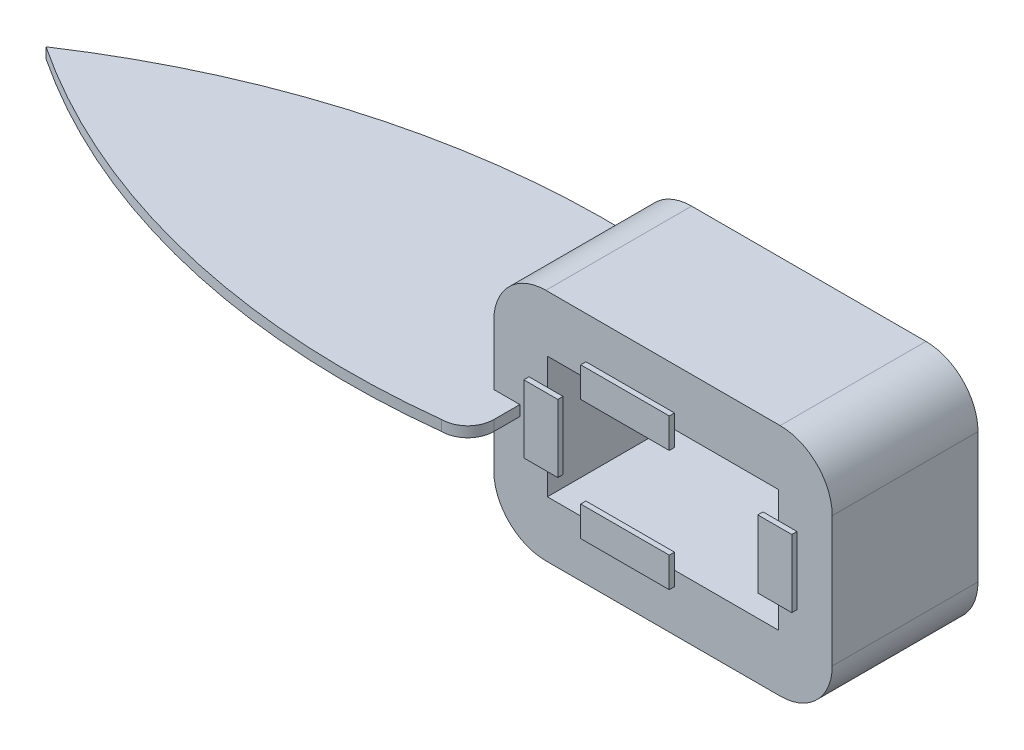
SolidWorks part; units mm, degrees
other "標示1"
sketch "草圖23" plane through (5.0653, 22.5, 33.0476) normal (0.0778, 0.9965, 0.0321) x (0.9968, -0.077, -0.0229)
ref_plane "前基準面" through (0, 0, 0) normal (0, 0, 1) x (1, 0, 0)
ref_plane "上基準面" through (0, 0, 0) normal (0, 1, 0) x (1, 0, 0)
ref_plane "右基準面" through (0, 0, 0) normal (1, 0, 0) x (0, 0, -1)
sketch "草圖1" plane through (0, 0, 0) normal (0, 0, 1) x (1, 0, 0)
  line L0 (-9.02, 0) -> (7.9922, 0) construction
  line L2 (-59.9347, 22.5) -> (5.0653, 22.5)
  line L3 (-59.9347, 22.5) -> (-59.9347, -22.5)
  line L4 (-59.9347, -22.5) -> (5.0653, -22.5)
  line L5 (5.0653, 22.5) -> (5.0653, -22.5)
  dimension "D1" = 45
  dimension "D2" = 22.5
  dimension "D3" = 65
extrude "填料-伸長1" add sketch "草圖1" along normal blind 28
sketch "草圖2" plane through (0, 0, 0) normal (0, 0, 1) x (1, 0, 0)
  line L0 (-59.9347, 0) -> (5.361, 0) construction
  line L1 (-59.9347, 22.5) -> (-59.9347, -22.5) construction
  line L2 (-27.4347, 22.5) -> (-27.4347, -22.5) construction
  line L3 (5.0653, 22.5) -> (-59.9347, 22.5) construction
  line L4 (-59.9347, -22.5) -> (5.0653, -22.5) construction
  line L6 (-49.6347, 11.7) -> (-5.2347, 11.7)
  line L7 (-49.6347, 11.7) -> (-49.6347, -11.7)
  line L8 (-49.6347, -11.7) -> (-5.2347, -11.7)
  line L9 (-5.2347, 11.7) -> (-5.2347, -11.7)
  dimension "D1" = 44.4
  dimension "D2" = 23.4
  dimension "D3" = 10.3
  dimension "D4" = 10.8
extrude "除料-伸長1" cut sketch "草圖2" along normal blind 39
ref_plane "平面1" through (0, 0, 28) normal (0, 0, 1) x (1, 0, 0)
sketch "草圖3" plane through (0, 0, 28) normal (0, 0, 1) x (1, 0, 0)
  line L0 (-59.9347, 22.5) -> (-59.9347, -22.5) construction
  line L2 (-59.9347, 12) -> (-55.9347, 12)
  line L3 (-59.9347, 12) -> (-59.9347, -12)
  line L4 (-59.9347, -12) -> (-55.9347, -12)
  line L5 (-55.9347, 12) -> (-55.9347, -12)
  line L8 (-5.2347, -11.7) -> (-49.6347, -11.7) construction
  dimension "D1" = 4
  dimension "D2" = 24
  dimension "D3" = 0.3
ref_plane "平面2" through (-59.9347, 0, 0) normal (-1, 0, 0) x (0, 0, 1)
sketch "草圖6" plane through (0, 0, 28) normal (0, 0, 1) x (1, 0, 0)
  line L0 (-15.2347, 0.3) -> (5.0653, -22.5)
  line L1 (-5.2347, 11.7) -> (-5.2347, -11.7) construction
  line L2 (-5.2347, -11.7) -> (-49.6347, -11.7) construction
  line L3 (-15.2347, 0.3) -> (-15.2347, -22.5)
  line L4 (-59.9347, -22.5) -> (5.0653, -22.5) construction
  line L5 (-15.2347, -22.5) -> (5.0653, -22.5)
  dimension "D1" = 10
  dimension "D2" = 12
ref_plane "平面4" through (0, 0, 0) normal (0, 0, -1) x (-1, 0, 0)
fillet "圓角1" radius 10 1 edges at (-59.9347, -22.5, 14) type face fillet first side face at (-59.9347, 0, 14) second side face at (-27.4347, -22.5, 14)
fillet "圓角2" radius 10 1 edges at (-59.9347, 22.5, 14) type face fillet first side face at (-27.4347, 22.5, 14) second side face at (-59.9347, 5, 14)
fillet "圓角3" radius 10 1 edges at (5.0653, 22.5, 14) type face fillet first side face at (-22.4347, 22.5, 14) second side face at (5.0653, 0, 14)
fillet "圓角4" radius 10 1 edges at (5.0653, -22.5, 14) type face fillet first side face at (-22.4347, -22.5, 14) second side face at (5.0653, -5, 14)
ref_plane "平面6" through (0, 0, 29) normal (0, 0, 1) x (1, 0, 0)
sketch "草圖10" plane through (0, 0, 29) normal (0, 0, 1) x (1, 0, 0)
  line L6 (-49.6347, 0) -> (-4.2092, 0) construction
  line L7 (-49.6347, -11.7) -> (-49.6347, 11.7) construction
  line L8 (-27.4347, -11.7) -> (-27.4347, 19.297) construction
  line L9 (-5.2347, -11.7) -> (-49.6347, -11.7) construction
  line L11 (-49.6347, 6.5) -> (-53.1651, 6.5)
  line L14 (-53.1651, 6.5) -> (-53.1651, -6.5)
  line L17 (-49.6347, 6.5) -> (-46.6347, 6.5)
  line L18 (-46.6347, 6.5) -> (-46.6347, -6.5)
  line L20 (-42.2347, -11.7) -> (-42.2347, -8.7)
  line L25 (-42.2347, -11.7) -> (-42.2347, -14.4546)
  line L27 (-8.2347, 6.5) -> (-8.2347, -6.5)
  line L28 (-8.2347, -6.5) -> (-5.2347, -6.5)
  line L29 (-5.2347, -6.5) -> (-1.7043, -6.5)
  line L30 (-1.7043, 6.5) -> (-1.7043, -6.5)
  line L32 (-25.2347, 8.7) -> (-25.2347, 14.4546)
  line L33 (-25.2347, -14.4546) -> (-25.2347, -8.7)
  line L34 (-25.2347, -14.4546) -> (-42.2347, -14.4546)
  line L35 (-25.2347, -8.7) -> (-42.2347, -8.7)
  line L36 (-25.2347, 8.7) -> (-42.2347, 8.7)
  line L37 (-25.2347, 14.4546) -> (-42.2347, 14.4546)
  line L38 (-42.2347, 8.7) -> (-42.2347, 14.4546)
  line L39 (-46.6347, -6.5) -> (-53.1651, -6.5)
  line L40 (-1.7043, 6.5) -> (-8.2347, 6.5)
  dimension "D3" = 13
  dimension "D4" = 6.5
extrude "填料-伸長6" add sketch "草圖10" against normal blind 1 separate body
sketch "草圖19" plane through (0, 0, 0) normal (0, 1, 0) x (1, 0, 0)
  line L0 (-59.9347, 6.325) -> (-59.9347, -6.325) construction
  line L1 (-59.9347, 1.0971) -> (-54.9347, 1.0971)
  line L2 (-59.9347, 1.0971) -> (-59.9347, -29)
  line L3 (-59.9347, -29) -> (-54.9347, -29)
  line L4 (-54.9347, 1.0971) -> (-54.9347, -29)
  line L5 (-24.75, -29) -> (24.75, -29) construction
  dimension "D1" = 5
ref_plane "平面7" through (0, 0, 28) normal (0, 0, 1) x (1, 0, 0)
sketch "草圖20" plane through (0, 0, 28) normal (0, 0, 1) x (1, 0, 0)
  line L0 (-59.9347, 12.5) -> (-59.9347, -12.5) construction
  line L1 (-59.9347, 1) -> (-54.932, 1)
  line L2 (-59.9347, 1) -> (-59.9347, -1)
  line L3 (-59.9347, -1) -> (-54.932, -1)
  line L4 (-54.932, 1) -> (-54.932, -1)
  line L5 (-59.9347, 0) -> (-54.9347, 0) construction
  dimension "D1" = 5.0026
  dimension "D2" = 2
  dimension "D3" = 1
extrude "填料-伸長7" add sketch "草圖20" along normal blind 10
ref_plane "平面8" through (0, 0, 0) normal (0, 0, -1) x (-1, 0, 0)
sketch "草圖21" plane through (0, 0, 0) normal (0, 0, -1) x (-1, 0, 0)
  line L0 (59.9347, 0) -> (54.9347, 0) construction
  line L1 (54.9323, 1) -> (59.9347, 1)
  line L2 (54.9323, 1) -> (54.9323, -1)
  line L3 (54.9323, -1) -> (59.9347, -1)
  line L4 (59.9347, 1) -> (59.9347, -1)
  dimension "D1" = 5.0023
  dimension "D2" = 2
  dimension "D3" = 1
extrude "填料-伸長8" add sketch "草圖21" along normal blind 10
sketch "草圖22" plane through (0, 0, 0) normal (0, 1, 0) x (1, 0, 0)
  line L1 (-59.9347, 10) -> (-59.9347, -38)
  line L2 (-59.9347, -14) -> (-159.9347, -14) construction
  arc A2 (-159.9347, -14) -> (-59.9347, 10) centre (-77.0498, -139.0204) cw
  arc A3 (-159.9347, -14) -> (-59.9347, -38) centre (-77.0498, 111.0204) ccw
  dimension "D2" = 150
  dimension "D3" = 150
  dimension "D1" = 100
extrude "填料-伸長9" add sketch "草圖22" along normal blind 1 and the other way blind 1
fillet "圓角5" radius 5 1 edges at (-54.9323, 0, -10) type face fillet first side face at (-57.4335, 0, -10) second side face at (-54.9323, 0, -5)
fillet "圓角6" radius 5 1 edges at (-54.932, 0, 38) type face fillet first side face at (-57.4333, 0, 38) second side face at (-54.932, 0, 33)
